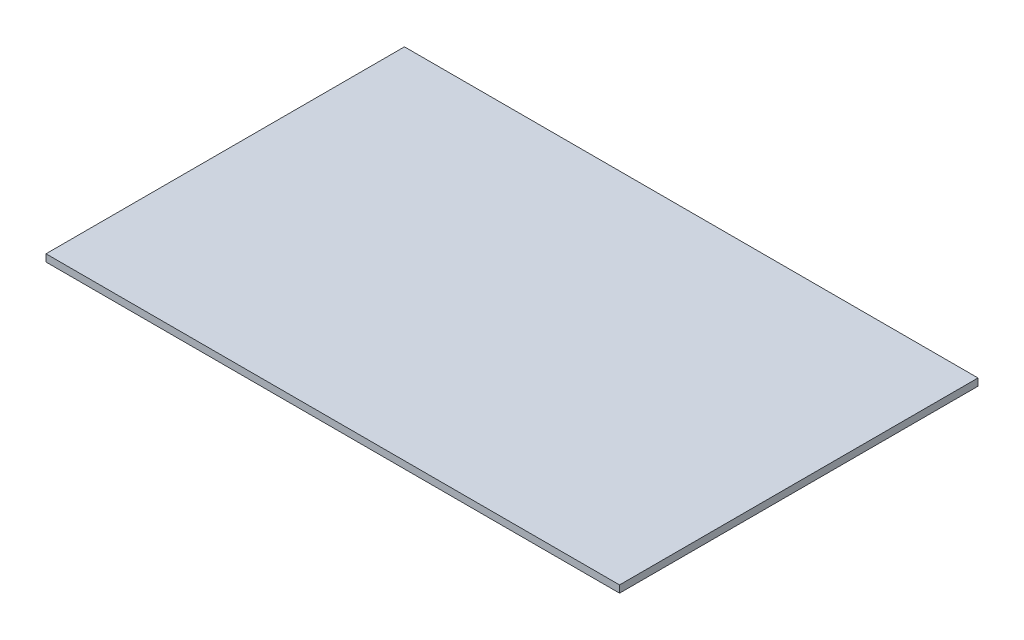
SolidWorks part; units mm, degrees
ref_plane "Спереди" through (0, 0, 0) normal (0, 0, 1) x (1, 0, 0)
ref_plane "Сверху" through (0, 0, 0) normal (0, 1, 0) x (1, 0, 0)
ref_plane "Справа" through (0, 0, 0) normal (1, 0, 0) x (0, 0, -1)
sketch "Эскиз1" plane through (0, 0, 0) normal (0, 1, 0) x (1, 0, 0)
  line L5 (0, 0) -> (160, 0)
  line L6 (0, 0) -> (0, 100)
  line L7 (0, 100) -> (160, 100)
  line L8 (160, 0) -> (160, 100)
  dimension "D1" = 160
  dimension "D2" = 100
extrude "Бобышка-Вытянуть1" add sketch "Эскиз1" along normal blind 2
